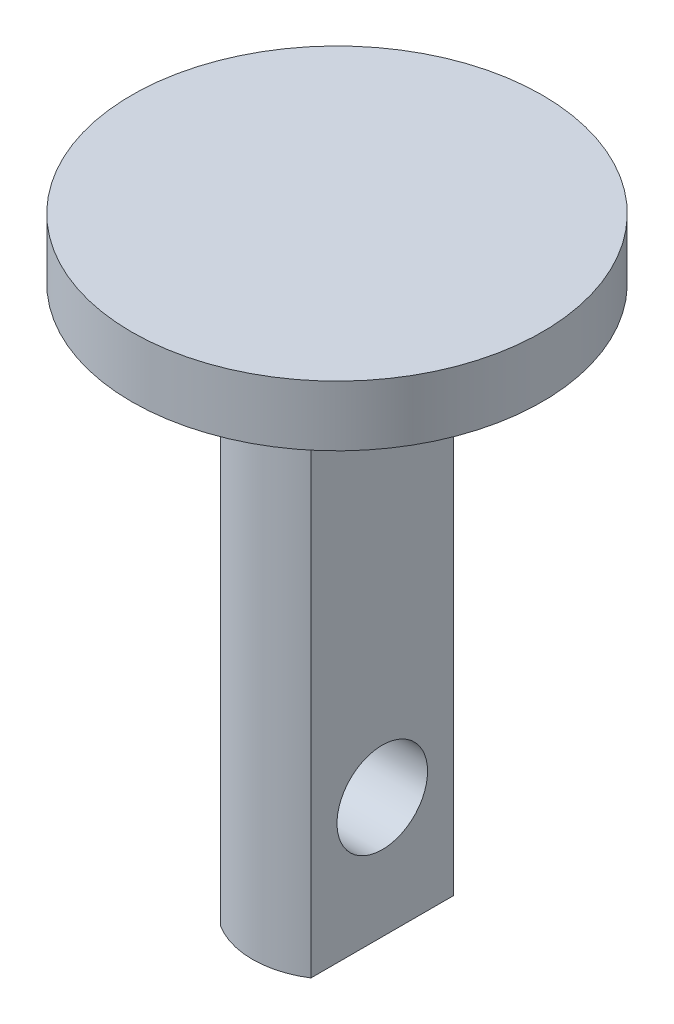
SolidWorks part; units mm, degrees
ref_plane "Front Plane" through (0, 0, 0) normal (0, 0, 1) x (1, 0, 0)
ref_plane "Top Plane" through (0, 0, 0) normal (0, 1, 0) x (1, 0, 0)
ref_plane "Right Plane" through (0, 0, 0) normal (1, 0, 0) x (0, 0, -1)
sketch "Sketch1" plane through (0, 0, 0) normal (0, 1, 0) x (1, 0, 0)
  line L1 (3.75, -16.5812) -> (-3.75, -16.5812)
  line L2 (3.75, -16.5812) -> (3.75, 16.5812)
  line L3 (3.75, 16.5812) -> (-3.75, 16.5812)
  line L4 (-3.75, -16.5812) -> (-3.75, 16.5812)
  line L5 (3.75, -16.5812) -> (-3.75, 16.5812) construction
  line L6 (3.75, 16.5812) -> (-3.75, -16.5812) construction
  circle A0 centre (0, 0) radius 17
  circle A1 centre (0, 0) radius 7
  dimension "D1" = 34
  dimension "D3" = 14
  dimension "D2" = 7.5
extrude "Boss-Extrude1" add sketch "Sketch1" against normal blind 5 contours A0
extrude "Boss-Extrude2" add sketch "Sketch1<3>" against normal blind 45 from surface contours L2 A1 L4 region at (0, 0, 0) starting at face at (0, -5, 17)
sketch "Sketch1<3>" plane through (0, 0, 0) normal (0, 1, 0) x (1, 0, 0) same geometry as "Sketch1"
sketch "Sketch2" plane through (3.75, 0, 0) normal (1, 0, 0) x (0, 0, -1)
  circle A0 centre (0, -40) radius 3.75
  point P2 (0, 0)
  point P4 (0, 0)
  dimension "D1" = 7.5
  dimension "D2" = 40
extrude "Cut-Extrude1" cut sketch "Sketch2" against normal through all
